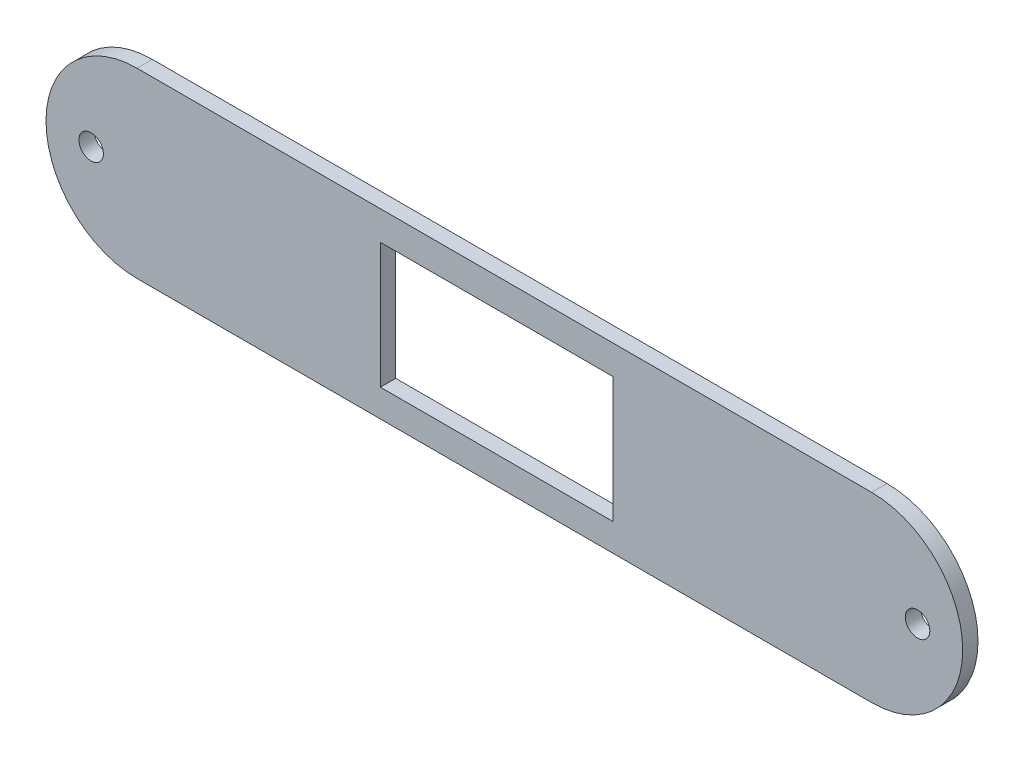
SolidWorks part; units mm, degrees
ref_plane "Front Plane" through (0, 0, 0) normal (0, 0, 1) x (1, 0, 0)
ref_plane "Top Plane" through (0, 0, 0) normal (0, 1, 0) x (1, 0, 0)
ref_plane "Right Plane" through (0, 0, 0) normal (1, 0, 0) x (0, 0, -1)
sketch "Sketch1" plane through (0, 0, 0) normal (0, 0, 1) x (1, 0, 0)
  line L0 (0, 0) -> (0, 16.0369) construction
  line L1 (30.5, 0) -> (-30.5, 0) construction
  line L2 (24, 6.5) -> (-24, 6.5)
  line L3 (24, -6.5) -> (-24, -6.5)
  line L4 (0, 0) -> (0, -11.8688) construction
  line L5 (24, 5.5) -> (-24, 5.5)
  line L6 (-24, -5.5) -> (24, -5.5)
  line L7 (27, 1.7) -> (27.7947, 1.7)
  line L8 (26, 0.5) -> (26, 0.7)
  line L9 (-26, -0.5) -> (-26.441, -0.5)
  line L10 (-26.441, 0.5) -> (-26, 0.5)
  line L11 (-26, -5.1235) -> (-26, -3.375)
  line L12 (-26, -3.375) -> (-26.5557, -3.375)
  line L13 (-26.5557, -2.325) -> (-26, -2.325)
  line L14 (-26, -2.325) -> (-26, -0.5)
  line L15 (-26, 0.5) -> (-26, 0.7)
  line L16 (-27, 1.7) -> (-27.7947, 1.7)
  line L17 (26, -2.325) -> (26, -0.5)
  line L18 (26.5557, -2.325) -> (26, -2.325)
  line L19 (26, -3.375) -> (26.5557, -3.375)
  line L20 (26, -5.1235) -> (26, -3.375)
  line L21 (26.441, 0.5) -> (26, 0.5)
  line L22 (26, -0.5) -> (26.441, -0.5)
  arc A0 (-24, 6.5) -> (-24, -6.5) centre (-24, 0) ccw
  arc A1 (-24, 5.5) -> (-28.5372, 3.1087) centre (-24, 0) ccw
  arc A2 (-26.5557, -2.325) -> (-26.5557, -3.375) centre (-27.465, -2.85) ccw
  arc A3 (-26.441, 0.5) -> (-26.441, -0.5) centre (-27, 0) ccw
  arc A4 (-27, 1.7) -> (-26, 0.7) centre (-27, 0.7) cw
  arc A5 (-26, -5.1235) -> (-24, -5.5) centre (-24, 0) ccw
  arc A6 (-27.7947, 1.7) -> (-28.5372, 3.1087) centre (-27.7947, 2.6) cw
  arc A7 (27.7947, 1.7) -> (28.5372, 3.1087) centre (27.7947, 2.6) ccw
  arc A8 (26, -5.1235) -> (24, -5.5) centre (24, 0) cw
  arc A9 (27, 1.7) -> (26, 0.7) centre (27, 0.7) ccw
  arc A10 (26.441, 0.5) -> (26.441, -0.5) centre (27, 0) cw
  arc A11 (26.5557, -2.325) -> (26.5557, -3.375) centre (27.465, -2.85) cw
  arc A12 (24, 5.5) -> (28.5372, 3.1087) centre (24, 0) cw
  arc A13 (24, 6.5) -> (24, -6.5) centre (24, 0) cw
  point P6 (0, 6.5)
  point P10 (0, -6.5)
  point P15 (0, 5.5)
  point P23 (-30.5, 0)
  point P56 (0, -5.5)
  dimension "D2" = 6.5
  dimension "D4" = 5.5
  dimension "D5" = 2.1
  dimension "D6" = 1.5
  dimension "D7" = 27
  dimension "D8" = 30.5
  dimension "D16" = 1
  dimension "D17" = 0.9
  dimension "D19" = 1.7
  dimension "D1" = 13
  dimension "D3" = 1
  dimension "D9" = 27.465
  dimension "D10" = 1
  dimension "D11" = 0.5
  dimension "D12" = 26
  dimension "D13" = 1.05
  dimension "D14" = 0.525
  dimension "D15" = 3.65
  dimension "D20" = 1
extrude "Boss-Extrude1" [suppressed] add sketch "Sketch1" along normal blind 25 and the other way blind 25
sketch "Sketch2" [suppressed] plane through (0, 0, 25) normal (0, 0, 1) x (1, 0, 0)
  line L0 (24, 6.5) -> (-24, 6.5) construction
  line L1 (-24, -6.5) -> (24, -6.5) construction
  line L2 (24, 6.5) -> (-24, 6.5) construction
  line L3 (-24, -6.5) -> (24, -6.5) construction
  line L4 (24, 6) -> (-24, 6)
  line L5 (-24, -6) -> (24, -6)
  arc A0 (-24, 6.5) -> (-24, -6.5) centre (-24, 0) ccw construction
  arc A1 (24, -6.5) -> (24, 6.5) centre (24, 0) ccw construction
  arc A2 (-24, 6.5) -> (-24, -6.5) centre (-24, 0) ccw construction
  arc A3 (24, -6.5) -> (24, 6.5) centre (24, 0) ccw construction
  arc A4 (-24, 6) -> (-24, -6) centre (-24, 0) ccw
  arc A5 (24, -6) -> (24, 6) centre (24, 0) ccw
  dimension "D1" = 0.5
sketch "Sketch3" plane through (0, 0, 0) normal (0, 0, 1) x (1, 0, 0)
  line L2 (24, 5.95) -> (-24, 5.95)
  line L3 (-24, -5.95) -> (24, -5.95)
  line L4 (-24, 0) -> (24, 0) construction
  line L5 (0, 5.95) -> (0, -5.95) construction
  arc A2 (-24, 5.95) -> (-24, -5.95) centre (-24, 0) ccw
  arc A3 (24, -5.95) -> (24, 5.95) centre (24, 0) ccw
  point P12 (0, 0)
  point P13 (0, -5.95)
  point P15 (0, 5.95)
  point P18 (0, 0)
  dimension "D2" = 5.95
  dimension "D3" = 11.9
  dimension "D1" = 48
extrude "Boss-Extrude2" add sketch "Sketch3" along normal blind 1
sketch "Sketch4" plane through (0, 0, 1) normal (0, 0, 1) x (1, 0, 0)
  line L0 (-27, 0) -> (27, 0) construction
  circle A0 centre (-27, 0) radius 0.8
  circle A1 centre (27, 0) radius 0.8
  point P4 (0, 0)
  dimension "D1" = 1.6
  dimension "D2" = 27
extrude "Cut-Extrude1" cut sketch "Sketch4" against normal through all contours A0 | A1
sketch "Sketch5" plane through (0, 0, 1) normal (0, 0, 1) x (1, 0, 0)
  line L0 (-24, -5.95) -> (24, -5.95) construction
  line L1 (-8.1, -4.15) -> (7.1, -4.15)
  line L2 (-8.1, -4.15) -> (-8.1, 4.05)
  line L3 (-8.1, 4.05) -> (7.1, 4.05)
  line L4 (7.1, -4.15) -> (7.1, 4.05)
  dimension "D1" = 15.2
  dimension "D2" = 8.2
  dimension "D3" = 1.8
  dimension "D4" = 7.1
extrude "Cut-Extrude2" cut sketch "Sketch5" against normal through all
